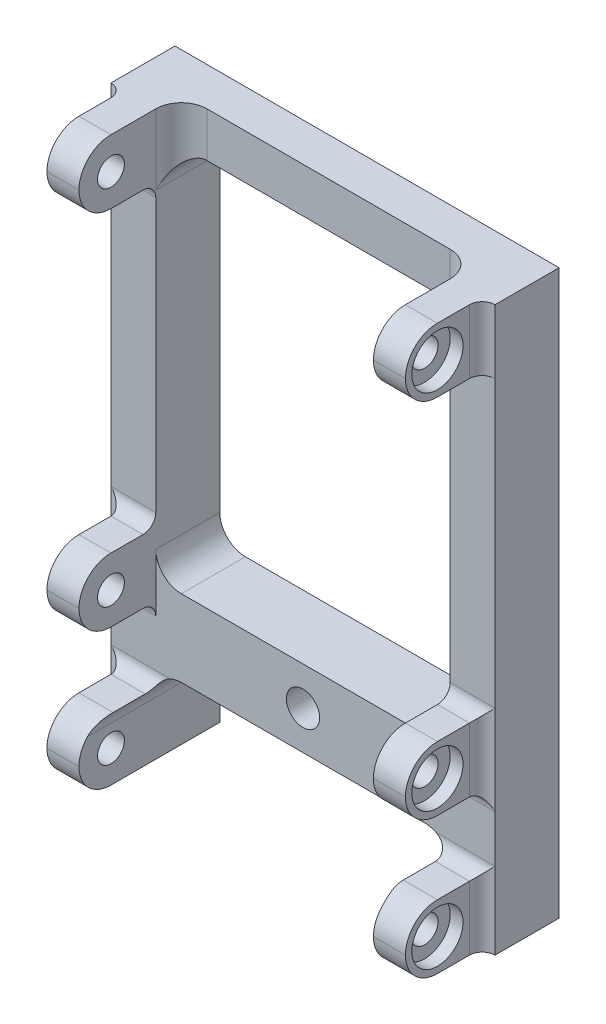
SolidWorks part; units mm, degrees
material "Esun Hard Tough Resin"
ref_plane "Front Plane" through (0, 0, 0) normal (0, 0, 1) x (1, 0, 0)
ref_plane "Top Plane" through (0, 0, 0) normal (0, 1, 0) x (1, 0, 0)
ref_plane "Right Plane" through (0, 0, 0) normal (1, 0, 0) x (0, 0, -1)
sketch "Sketch2" plane through (0, 0, 0) normal (0, 0, 1) x (1, 0, 0)
  line L1 (-15, -22) -> (15, -22)
  line L2 (-15, -22) -> (-15, 22)
  line L3 (-15, 22) -> (15, 22)
  line L4 (15, -22) -> (15, 22)
  line L5 (-15, -22) -> (15, 22) construction
  line L6 (-15, 22) -> (15, -22) construction
  line L7 (-11.5, -22) -> (11.5, -22)
  line L8 (-11.5, -22) -> (-11.5, 22)
  line L9 (-11.5, 22) -> (11.5, 22)
  line L10 (11.5, -22) -> (11.5, 22)
  line L11 (-11.5, -22) -> (11.5, 22) construction
  line L12 (-11.5, 22) -> (11.5, -22) construction
  point P0 (0, 0)
  point P6 (0, 0)
  dimension "D1" = 44
  dimension "D2" = 30
  dimension "D3" = 23
extrude "Boss-Extrude1" add sketch "Sketch2" along normal blind 5 contours L1 L8 L3 L2 | L10 L1 L4 L3 region at (-13.25, 0, 0) region at (13.25, 0, 0)
sketch "Sketch3" plane through (0, 0, 0) normal (0, 0, -1) x (-1, 0, 0)
  line L0 (15, -22) -> (15, 22) construction
  line L1 (-15, 22) -> (15, 22)
  line L2 (-15, 22) -> (-15, 18.5)
  line L3 (-15, 18.5) -> (15, 18.5)
  line L4 (15, 22) -> (15, 18.5)
  dimension "D1" = 3.5
extrude "Boss-Extrude2" add sketch "Sketch3" against normal blind 3
sketch "Sketch4" plane through (0, 0, 5) normal (0, 0, 1) x (1, 0, 0)
  line L0 (-11.5, -22) -> (-11.5, 22) construction
  line L1 (-11.5, 22) -> (-14, 22)
  line L2 (-11.5, 22) -> (-11.5, 17)
  line L3 (-11.5, 17) -> (-14, 17)
  line L4 (-14, 22) -> (-14, 17)
  line L5 (-11.5, -6.3) -> (-14, -6.3)
  line L6 (-11.5, -6.3) -> (-11.5, -11.3)
  line L7 (-11.5, -11.3) -> (-14, -11.3)
  line L8 (-14, -6.3) -> (-14, -11.3)
  line L10 (-11.5, -17) -> (-14, -17)
  line L11 (-11.5, -17) -> (-11.5, -22)
  line L12 (-11.5, -22) -> (-14, -22)
  line L13 (-14, -17) -> (-14, -22)
  line L14 (0, -1000.6568) -> (0, 48999.3432) construction
  line L15 (11.5, -22) -> (14, -22)
  line L16 (14, -17) -> (14, -22)
  line L17 (11.5, -17) -> (14, -17)
  line L18 (11.5, -17) -> (11.5, -22)
  line L19 (11.5, -11.3) -> (14, -11.3)
  line L20 (14, -6.3) -> (14, -11.3)
  line L21 (11.5, -6.3) -> (14, -6.3)
  line L22 (11.5, -6.3) -> (11.5, -11.3)
  line L23 (11.5, 17) -> (14, 17)
  line L24 (14, 22) -> (14, 17)
  line L25 (11.5, 22) -> (14, 22)
  line L26 (11.5, 22) -> (11.5, 17)
  point P15 (-14, 19.5)
  point P16 (-14, -8.8)
  point P17 (-11.5, -8.8)
  point P18 (-11.5, -19.5)
  dimension "D1" = 2.5
  dimension "D2" = 2.5
  dimension "D3" = 2.5
  dimension "D4" = 5
  dimension "D5" = 5
  dimension "D6" = 5
  dimension "D7" = 28.3
  dimension "D8" = 10.7
extrude "Boss-Extrude3" add sketch "Sketch4" along normal blind 6
sketch "Sketch5" plane through (-14, 0, 0) normal (-1, 0, 0) x (0, 0, 1)
  line L1 (11, 22) -> (11, 17) construction
  line L3 (11, -6.3) -> (11, -11.3) construction
  line L5 (11, -17) -> (11, -22) construction
  circle A0 centre (8.5, 19.5) radius 1.05
  circle A1 centre (8.5, -8.8) radius 1.05
  circle A2 centre (8.5, -19.5) radius 1.05
  point P8 (11, 19.5)
  point P17 (11, -8.8)
  point P23 (11, -19.5)
  dimension "D1" = 2.1
  dimension "D2" = 2.1
  dimension "D3" = 2.1
  dimension "D4" = 2.5
extrude "Cut-Extrude1" cut sketch "Sketch5" against normal through all
fillet "Fillet1" radius 2.5 12 edges at (12.75, -17, 11) (12.75, -22, 11) (12.75, -6.3, 11) (12.75, -11.3, 11) (-12.75, -22, 11) (-12.75, -17, 11) (-12.75, -11.3, 11) (-12.75, -6.3, 11) (-12.75, 17, 11) (-12.75, 22, 11) (12.75, 22, 11) (12.75, 17, 11)
fillet "Fillet2" radius 2 4 edges at (-11.5, 18.5, 1.5) (11.5, 18.5, 1.5) (11.5, 20.25, 3) (-11.5, 20.25, 3)
sketch "Sketch6" plane through (0, 0, 0) normal (0, 0, -1) x (-1, 0, 0)
  line L0 (-11.5, -22) -> (-15, -22) construction
  line L1 (11.5, -22) -> (11.5, 16.5) construction
  line L2 (-11.5, -15.8) -> (11.5, -15.8)
  line L3 (-11.5, -15.8) -> (-11.5, -9.8)
  line L4 (-11.5, -9.8) -> (11.5, -9.8)
  line L5 (11.5, -15.8) -> (11.5, -9.8)
  line L6 (-11.5, -15.8) -> (11.5, -9.8) construction
  line L7 (-11.5, -9.8) -> (11.5, -15.8) construction
  circle A0 centre (0, -12.8) radius 1.3
  dimension "D2" = 2.6
  dimension "D1" = 9.2
  dimension "D3" = 6
extrude "Boss-Extrude4" add sketch "Sketch6" against normal up to surface (5 mm away) up to face at (13.1923, -1.4385, 5)
fillet "Fillet3" radius 2 4 edges at (-11.5, -15.8, 2.5) (11.5, -15.8, 2.5) (11.5, -9.8, 2.5) (-11.5, -9.8, 2.5)
sketch "Sketch7" plane through (-14, 0, 0) normal (-1, 0, 0) x (0, 0, 1)
  circle A0 centre (8.5, 19.5) radius 2
  circle A1 centre (8.5, -8.8) radius 2
  circle A2 centre (8.5, -19.5) radius 2
  dimension "D1" = 4
  dimension "D2" = 4
  dimension "D3" = 4
extrude "Cut-Extrude2" cut sketch "Sketch7" against normal blind 1
mirror "Mirror1" about plane through (0, 0, 0) normal (1, 0, 0) of "Cut-Extrude2"
fillet "Fillet4" radius 1 13 edges at (12.75, -11.3, 5) (-12.75, -11.3, 5) (-12.75, 17, 5) (14, -19.5, 5) (14, -8.8, 5) (14, 19.5, 5) (-12.75, -6.3, 5) (-12.6665, -17, 5) (-14, -19.5, 5) (-14, -8.8, 5) (12.6665, -17, 5) (12.75, -6.3, 5) (-14, 19.5, 5)
equation "\"D2@Sketch4\"=\"D1@Sketch4\""
equation "\"D3@Sketch4\"=\"D1@Sketch4\""
equation "\"D5@Sketch4\"=\"D4@Sketch4\""
equation "\"D6@Sketch4\"=\"D4@Sketch4\""
equation "\"D2@Sketch5\"=\"D1@Sketch5\""
equation "\"D3@Sketch5\"=\"D1@Sketch5\""
equation "\"D2@Sketch7\"=\"D1@Sketch7\""
equation "\"D3@Sketch7\"=\"D1@Sketch7\""
